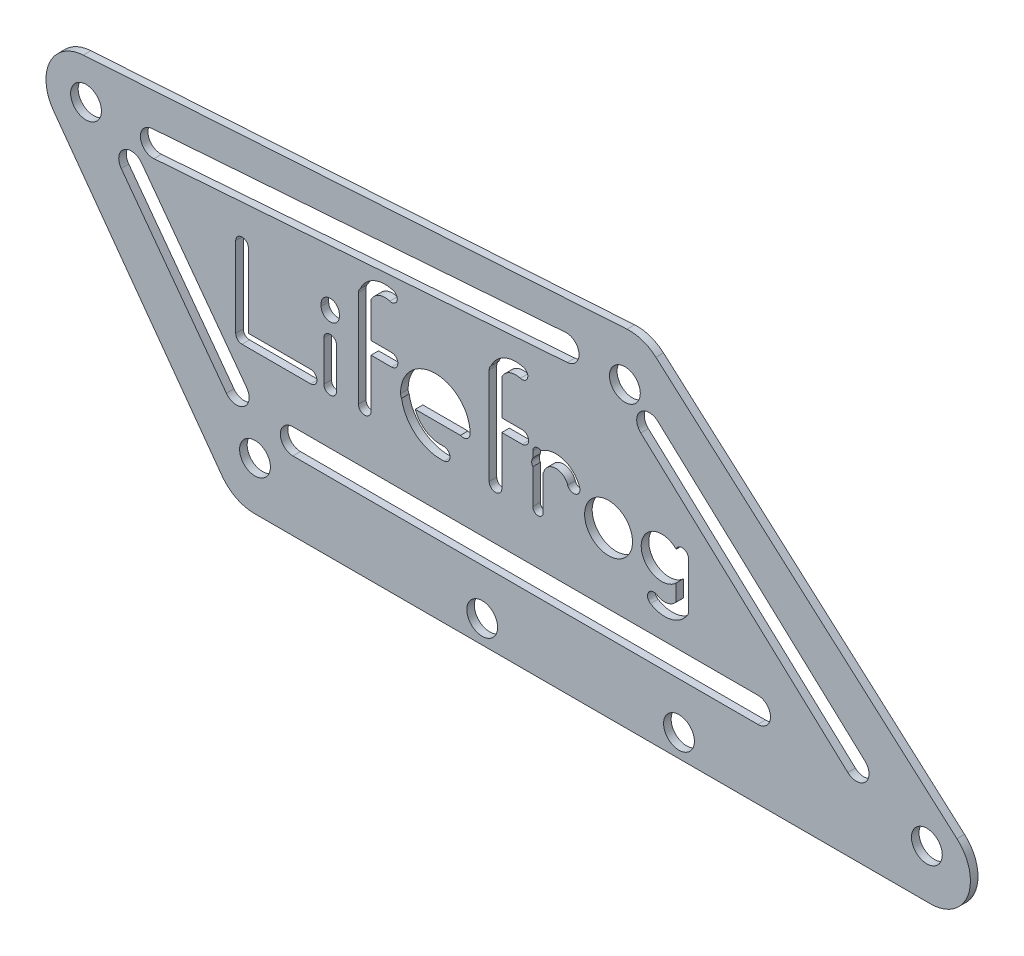
SolidWorks part; units mm, degrees
ref_plane "Front Plane" through (0, 0, 0) normal (0, 0, 1) x (1, 0, 0)
ref_plane "Top Plane" through (0, 0, 0) normal (0, 1, 0) x (1, 0, 0)
ref_plane "Right Plane" through (0, 0, 0) normal (1, 0, 0) x (0, 0, -1)
sketch "Sketch3" plane through (0, 0, 0) normal (0, 0, 1) x (1, 0, 0)
  line L0 (-105.0544, 1.9987) -> (28.8099, 1.9987)
  line L3 (-144.7818, 51.1553) -> (-111.4337, 5.2494)
  line L4 (-130.8953, -6.016) -> (39.056, -6.016)
  line L5 (-138.4025, 55.7894) -> (-31.7004, 60.7894) construction
  line L6 (-138.4025, 55.7894) -> (-31.7004, 55.7894) construction
  line L7 (-138.9015, 63.6585) -> (-31.2776, 70.4842)
  line L8 (-25.5532, 68.52) -> (34.0353, 15.7884)
  line L9 (-31.7004, 55.7894) -> (-31.7004, 60.7894) construction
  line L10 (-104.9148, 11.5444) -> (-59.9429, 6.5523) construction
  line L11 (-59.9429, 6.5523) -> (-105.0544, 6.5523) construction
  line L12 (-105.0544, 6.5523) -> (-104.9148, 11.5444) construction
  arc A0 (28.8099, 1.9987) -> (34.0353, 15.7884) centre (28.8099, 9.8836) ccw
  arc A1 (-25.5532, 68.52) -> (-31.2776, 70.4842) centre (-30.7786, 62.6152) ccw
  arc A2 (-105.0544, 1.9987) -> (-111.4337, 5.2494) centre (-105.0544, 9.8836) cw
  arc A3 (-144.7818, 51.1553) -> (-138.9015, 63.6585) centre (-138.4025, 55.7894) cw
  circle A11 centre (49.307, 58.8735) radius 21
  circle A13 centre (-59.9429, 6.5523) radius 3.05
  circle A14 centre (-104.9148, 11.5444) radius 3.05
  circle A15 centre (-20.9941, 6.4971) radius 3.05
  circle A16 centre (28.0724, 11.5486) radius 3.05
  circle A17 centre (-31.7004, 60.7894) radius 3.05
  circle A18 centre (-138.3619, 55.8478) radius 3.05
  dimension "D1" = 7.8849
  dimension "D2" = 6.1
  dimension "D3" = 4.9922
  dimension "D4" = 5
extrude "Boss-Extrude2" add sketch "Sketch3" along normal blind 1.5 contours A3 L3 A2 L0 A0 L8 A1 L7 A18 A17 A16 A15 A14 A13 region at (-58.2224, 33.7317, 0)
sketch "Sketch4" plane through (0, 0, 1.5) normal (0, 0, 1) x (1, 0, 0)
  line L1 (-26.8632, 55.8937) -> (14.1152, 18.1826) construction
  line L5 (-25.1703, 57.7333) -> (15.8082, 20.0221)
  line L9 (-28.5561, 54.0541) -> (12.4223, 16.343)
  line L13 (-97.4073, 18.1826) -> (-5.3775, 18.1826) construction
  line L23 (-129.3887, 49.4647) -> (-108.5686, 21.3307) construction
  line L26 (-127.3791, 50.9519) -> (-106.559, 22.8178)
  line L29 (-131.3983, 47.9776) -> (-110.5782, 19.8435)
  line L30 (-125.1067, 55.383) -> (-43.278, 61.3603) construction
  line L31 (-125.2888, 57.8764) -> (-43.4601, 63.8537)
  line L32 (-124.9246, 52.8897) -> (-43.0958, 58.867)
  line L33 (-97.4073, 20.6826) -> (-5.3775, 20.6826)
  line L34 (-97.4073, 15.6826) -> (-5.3775, 15.6826)
  line L35 (-107.4816, 46.9298) -> (-107.4816, 31.0422) construction
  line L36 (-106.2316, 46.9298) -> (-106.2316, 31.0422)
  line L37 (-108.7316, 46.9298) -> (-108.7316, 31.0422)
  line L38 (-107.4816, 31.0422) -> (-93.9009, 31.0422) construction
  line L39 (-107.4816, 32.2922) -> (-93.9009, 32.2922)
  line L40 (-107.4816, 29.7922) -> (-93.9009, 29.7922)
  line L41 (-90.0274, 38.986) -> (-90.0274, 31.0422) construction
  line L42 (-88.7774, 38.986) -> (-88.7774, 31.0422)
  line L43 (-91.2774, 38.986) -> (-91.2774, 31.0422)
  line L44 (-90.0274, 44.5942) -> (-90.0274, 44.1452) construction
  line L45 (-88.2261, 44.5942) -> (-88.2261, 44.1452)
  line L46 (-91.8287, 44.5942) -> (-91.8287, 44.1452)
  line L47 (-83.1958, 31.0422) -> (-83.1958, 50.1599) construction
  line L48 (-84.4458, 31.0422) -> (-84.4458, 50.1599)
  line L49 (-81.9458, 31.0422) -> (-81.9458, 50.1599)
  line L50 (-83.1958, 41.9365) -> (-77.886, 41.9365) construction
  line L51 (-83.1958, 43.1865) -> (-77.886, 43.1865)
  line L52 (-83.1958, 40.6865) -> (-77.886, 40.6865)
  line L53 (-74.7394, 37.0381) -> (-63.7024, 37.0381) construction
  line L54 (-74.7394, 38.2881) -> (-63.7024, 38.2881)
  line L55 (-74.7394, 35.7881) -> (-63.7024, 35.7881)
  line L56 (-57.316, 30.7325) -> (-57.316, 49.8502) construction
  line L57 (-58.566, 30.7325) -> (-58.566, 49.8502)
  line L58 (-56.066, 30.7325) -> (-56.066, 49.8502)
  line L59 (-57.316, 41.6268) -> (-52.0062, 41.6268) construction
  line L60 (-57.316, 42.8768) -> (-52.0062, 42.8768)
  line L61 (-57.316, 40.3768) -> (-52.0062, 40.3768)
  line L62 (-48.9003, 30.7325) -> (-48.9003, 40.2914) construction
  line L63 (-49.9346, 30.7325) -> (-49.9346, 40.2914)
  line L64 (-47.8659, 30.7325) -> (-47.8659, 40.2914)
  line L65 (-20.3592, 37.2289) -> (-20.3592, 28.1084) construction
  line L66 (-19.1092, 37.2289) -> (-19.1092, 28.1084)
  line L67 (-21.6092, 37.2289) -> (-21.6092, 28.1084)
  arc A16 (-127.3791, 50.9519) -> (-131.3983, 47.9776) centre (-129.3887, 49.4647) ccw
  arc A17 (-110.5782, 19.8435) -> (-106.559, 22.8178) centre (-108.5686, 21.3307) ccw
  arc A18 (-125.2888, 57.8764) -> (-124.9246, 52.8897) centre (-125.1067, 55.383) ccw
  arc A19 (-43.0958, 58.867) -> (-43.4601, 63.8537) centre (-43.278, 61.3603) ccw
  arc A20 (-25.1703, 57.7333) -> (-28.5561, 54.0541) centre (-26.8632, 55.8937) ccw
  arc A21 (12.4223, 16.343) -> (15.8082, 20.0221) centre (14.1152, 18.1826) ccw
  arc A22 (-97.4073, 20.6826) -> (-97.4073, 15.6826) centre (-97.4073, 18.1826) ccw
  arc A23 (-5.3775, 15.6826) -> (-5.3775, 20.6826) centre (-5.3775, 18.1826) ccw
  arc A24 (-106.2316, 46.9298) -> (-108.7316, 46.9298) centre (-107.4816, 46.9298) ccw
  arc A25 (-108.7316, 31.0422) -> (-106.2316, 31.0422) centre (-107.4816, 31.0422) ccw
  arc A26 (-107.4816, 32.2922) -> (-107.4816, 29.7922) centre (-107.4816, 31.0422) ccw
  arc A27 (-93.9009, 29.7922) -> (-93.9009, 32.2922) centre (-93.9009, 31.0422) ccw
  arc A28 (-88.7774, 38.986) -> (-91.2774, 38.986) centre (-90.0274, 38.986) ccw
  arc A29 (-91.2774, 31.0422) -> (-88.7774, 31.0422) centre (-90.0274, 31.0422) ccw
  arc A30 (-88.2261, 44.5942) -> (-91.8287, 44.5942) centre (-90.0274, 44.5942) ccw
  arc A31 (-91.8287, 44.1452) -> (-88.2261, 44.1452) centre (-90.0274, 44.1452) ccw
  arc A32 (-84.4458, 31.0422) -> (-81.9458, 31.0422) centre (-83.1958, 31.0422) ccw
  arc A33 (-81.9458, 50.1599) -> (-84.4458, 50.1599) centre (-83.1958, 50.1599) ccw
  arc A34 (-83.1958, 50.1599) -> (-77.886, 52.8897) centre (-79.176, 48.8699) cw construction
  arc A35 (-77.5399, 53.9683) -> (-84.2744, 50.5061) centre (-79.176, 48.8699) ccw
  arc A36 (-78.2322, 51.8111) -> (-82.1172, 49.8138) centre (-79.176, 48.8699) ccw
  arc A37 (-78.2322, 51.8111) -> (-77.5399, 53.9683) centre (-77.886, 52.8897) ccw
  arc A38 (-84.2744, 50.5061) -> (-82.1172, 49.8138) centre (-83.1958, 50.1599) ccw
  arc A39 (-83.1958, 43.1865) -> (-83.1958, 40.6865) centre (-83.1958, 41.9365) ccw
  arc A40 (-77.886, 40.6865) -> (-77.886, 43.1865) centre (-77.886, 41.9365) ccw
  arc A41 (-74.7394, 38.2881) -> (-74.7394, 35.7881) centre (-74.7394, 37.0381) ccw
  arc A42 (-63.7024, 35.7881) -> (-63.7024, 38.2881) centre (-63.7024, 37.0381) ccw
  arc A43 (-74.7394, 37.0381) -> (-63.7024, 37.0381) centre (-69.2209, 37.0381) cw construction
  arc A44 (-62.3325, 37.0381) -> (-76.1093, 37.0381) centre (-69.2209, 37.0381) ccw
  arc A45 (-65.0723, 37.0381) -> (-73.3696, 37.0381) centre (-69.2209, 37.0381) ccw
  arc A46 (-65.0723, 37.0381) -> (-62.3325, 37.0381) centre (-63.7024, 37.0381) ccw
  arc A47 (-76.1093, 37.0381) -> (-73.3696, 37.0381) centre (-74.7394, 37.0381) ccw
  arc A48 (-74.7394, 37.0381) -> (-67.5709, 31.0113) centre (-68.1417, 37.609) ccw construction
  arc A49 (-75.9848, 36.9304) -> (-67.4631, 29.766) centre (-68.1417, 37.609) ccw
  arc A50 (-73.4941, 37.1459) -> (-67.6786, 32.2567) centre (-68.1417, 37.609) ccw
  arc A51 (-73.4941, 37.1459) -> (-75.9848, 36.9304) centre (-74.7394, 37.0381) ccw
  arc A52 (-67.4631, 29.766) -> (-67.6786, 32.2567) centre (-67.5709, 31.0113) ccw
  arc A53 (-58.566, 30.7325) -> (-56.066, 30.7325) centre (-57.316, 30.7325) ccw
  arc A54 (-56.066, 49.8502) -> (-58.566, 49.8502) centre (-57.316, 49.8502) ccw
  arc A55 (-57.316, 49.8502) -> (-52.0438, 52.5918) centre (-53.2963, 48.5602) cw construction
  arc A56 (-51.7077, 53.6736) -> (-58.3946, 50.1964) centre (-53.2963, 48.5602) ccw
  arc A57 (-52.3798, 51.5101) -> (-56.2374, 49.5041) centre (-53.2963, 48.5602) ccw
  arc A58 (-52.3798, 51.5101) -> (-51.7077, 53.6736) centre (-52.0438, 52.5918) ccw
  arc A59 (-58.3946, 50.1964) -> (-56.2374, 49.5041) centre (-57.316, 49.8502) ccw
  arc A60 (-57.316, 42.8768) -> (-57.316, 40.3768) centre (-57.316, 41.6268) ccw
  arc A61 (-52.0062, 40.3768) -> (-52.0062, 42.8768) centre (-52.0062, 41.6268) ccw
  arc A62 (-49.9346, 30.7325) -> (-47.8659, 30.7325) centre (-48.9003, 30.7325) ccw
  arc A63 (-47.8659, 40.2914) -> (-49.9346, 40.2914) centre (-48.9003, 40.2914) ccw
  arc A64 (-48.9003, 38.2881) -> (-41.8429, 38.2881) centre (-45.3716, 37.1138) cw construction
  arc A65 (-40.6569, 38.6828) -> (-50.0863, 38.6828) centre (-45.3716, 37.1138) ccw
  arc A66 (-43.029, 37.8934) -> (-47.7142, 37.8934) centre (-45.3716, 37.1138) ccw
  arc A67 (-43.029, 37.8934) -> (-40.6569, 38.6828) centre (-41.8429, 38.2881) ccw
  arc A68 (-50.0863, 38.6828) -> (-47.7142, 37.8934) centre (-48.9003, 38.2881) ccw
  circle A69 centre (-34.9295, 34.565) radius 4.7404
  circle A71 centre (-24.4066, 34.7299) radius 4.0673
  arc A73 (-19.1092, 37.2289) -> (-21.6092, 37.2289) centre (-20.3592, 37.2289) ccw
  arc A74 (-21.6092, 28.1084) -> (-19.1092, 28.1084) centre (-20.3592, 28.1084) ccw
  arc A75 (-20.3592, 28.1084) -> (-25.9689, 26.8183) centre (-23.8091, 30.2683) cw construction
  arc A76 (-26.6322, 25.7588) -> (-19.2997, 27.4451) centre (-23.8091, 30.2683) ccw
  arc A77 (-25.3056, 27.8778) -> (-21.4187, 28.7717) centre (-23.8091, 30.2683) ccw
  arc A78 (-25.3056, 27.8778) -> (-26.6322, 25.7588) centre (-25.9689, 26.8183) ccw
  arc A79 (-19.2997, 27.4451) -> (-21.4187, 28.7717) centre (-20.3592, 28.1084) ccw
  point P3 (-118.9786, 35.3977)
  point P10 (-6.374, 37.0381)
  point P12 (-84.1923, 58.3717)
  point P23 (-51.3924, 18.1826)
  point P30 (-107.4816, 38.986)
  point P35 (-100.6912, 31.0422)
  point P42 (-90.0274, 35.0141)
  point P49 (-90.0274, 44.3697)
  point P56 (-83.1958, 40.6011)
  point P66 (-81.1063, 52.6245)
  point P73 (-80.5409, 41.9365)
  point P78 (-69.2209, 37.0381)
  point P88 (-69.2209, 42.5567)
  point P96 (-72.4033, 32.5401)
  point P101 (-57.316, 40.2914)
  point P111 (-55.244, 52.3058)
  point P118 (-54.6611, 41.6268)
  point P125 (-48.9003, 35.5119)
  point P133 (-45.3716, 40.8327)
  point P146 (-20.3592, 32.6687)
  point P154 (-22.8969, 26.3016)
extrude "Cut-Extrude6" cut sketch "Sketch4" against normal through all both and the other way through all contours A25 L36 A24 L37 | L40 A27 L39 A26 | L43 A28 L42 A29 | L46 A31 L45 A30 | L49 A33 L48 A32 | L52 A40 L51 A39 | A36 A38 A35 A37 | A45 A47 A44 A46 | L55 A42 L54 A41 | A50 A52 A49 A51 | L34 A23 L33 A22 | L57 A54 L58 A53 | L60 A61 L61 A60 | A56 A59 A57 A58 | A66 A68 A65 A67 | A69 | L64 A63 L63 A62 | A71 | L67 A74 L66 A73 | A77 A79 A76 A78 | L9 A21 L5 A20 | L32 A19 L31 A18 | L29 A17 L26 A16
sketch "Sketch5" plane through (0, 0, 1.5) normal (0, 0, 1) x (1, 0, 0)
  line L1 (-73.4557, 41.3578) -> (-64.6349, 41.3578)
  line L2 (-73.4557, 41.3578) -> (-73.4557, 37.3303)
  line L3 (-73.4557, 37.3303) -> (-64.6349, 37.3303)
  line L4 (-64.6349, 41.3578) -> (-64.6349, 37.3303)
extrude "Cut-Extrude7" cut sketch "Sketch5" against normal blind 10
